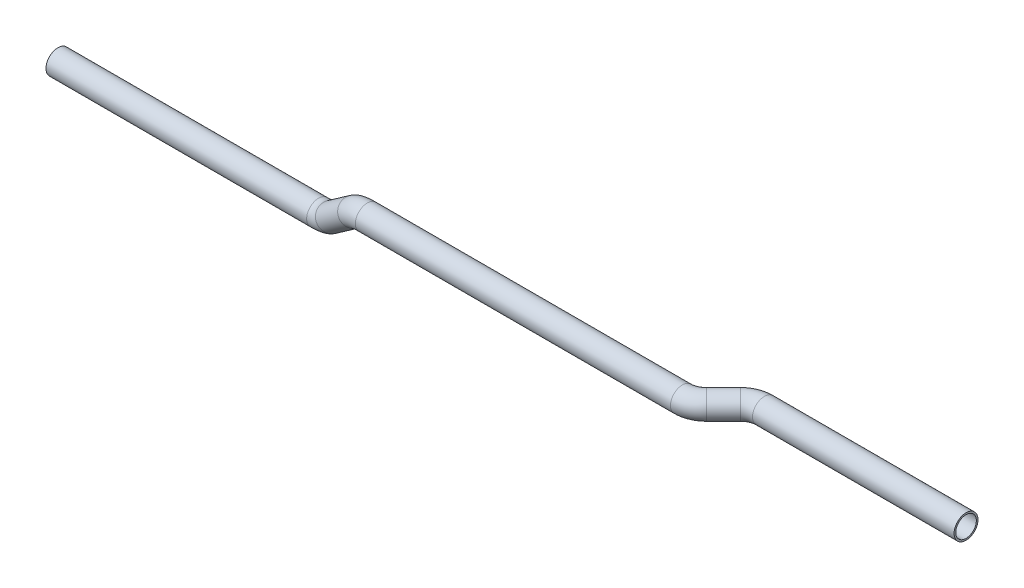
SolidWorks part; units mm, degrees
ref_plane "Front Plane" through (0, 0, 0) normal (0, 0, 1) x (1, 0, 0)
ref_plane "Top Plane" through (0, 0, 0) normal (0, 1, 0) x (1, 0, 0)
ref_plane "Right Plane" through (0, 0, 0) normal (1, 0, 0) x (0, 0, -1)
sketch3d "3DSketch2"
  line L0 (0, 0, 0) -> (138.3781, 0, 0)
  line L1 (0, 27.2535, 0) -> (0, 27.2535, 16.51) construction
  line L2 (0, 27.2535, 16.51) -> (467.4369, 27.2535, 16.51) construction
  line L3 (147.3584, 3.1815, 1.9273) -> (171.7832, 24.072, 14.5827)
  line L4 (375.0735, 27.2535, 0) -> (482.0986, 27.2535, 0)
  line L5 (0, 0, 0) -> (0, 27.2535, 0) construction
  line L6 (0, 27.2535, 0) -> (467.4369, 27.2535, 0) construction
  line L7 (180.7635, 27.2535, 16.51) -> (348.0425, 27.2535, 16.51)
  line L8 (357.0227, 27.2535, 12.7903) -> (366.0932, 27.2535, 3.7197)
  arc A0 (366.0932, 27.2535, 3.7197) -> (375.0735, 27.2535, 0) centre (375.0735, 27.2535, 12.7) ccw
  arc A1 (348.0425, 27.2535, 16.51) -> (357.0227, 27.2535, 12.7903) centre (348.0425, 27.2535, 3.81) ccw
  arc A2 (171.7832, 24.072, 14.5827) -> (180.7635, 27.2535, 16.51) centre (180.7635, 16.3912, 9.9297) ccw
  arc A3 (138.3781, 0, 0) -> (147.3584, 3.1815, 1.9273) centre (138.3781, 10.8623, 6.5803) ccw
  point P10 (369.813, 27.2535, 0)
  point P11 (375.0735, 14.5535, 12.7)
  point P14 (353.303, 27.2535, 16.51)
  point P15 (348.0425, 39.9535, 3.81)
  point P18 (175.503, 27.2535, 16.51)
  point P19 (180.7635, 22.9715, -0.9326)
  point P22 (143.6387, 0, 0)
  point P26 (138.3781, 4.282, 17.4426)
  dimension "D5" = 177.8
  dimension "D10" = 27.2535
  dimension "D7" = 12.7
  dimension "D1" = 143.6387
  dimension "D2" = 16.51
  dimension "D3" = 45
  dimension "D4" = 135
  dimension "D6" = 112.2856
  dimension "D11" = 467.4369
ref_plane "Plane1" through (0, 0, 0) normal (1, 0, 0) x (0, 0, -1)
sketch "Sketch1" plane through (0, 0, 0) normal (1, 0, 0) x (0, 0, -1)
  circle A0 centre (0, 0) radius 6.35
  circle A1 centre (0, 0) radius 5.461
  dimension "D1" = 12.7
  dimension "D2" = 0.889
sweep "Sweep2" add profiles "Sketch1" path "3DSketch2"
